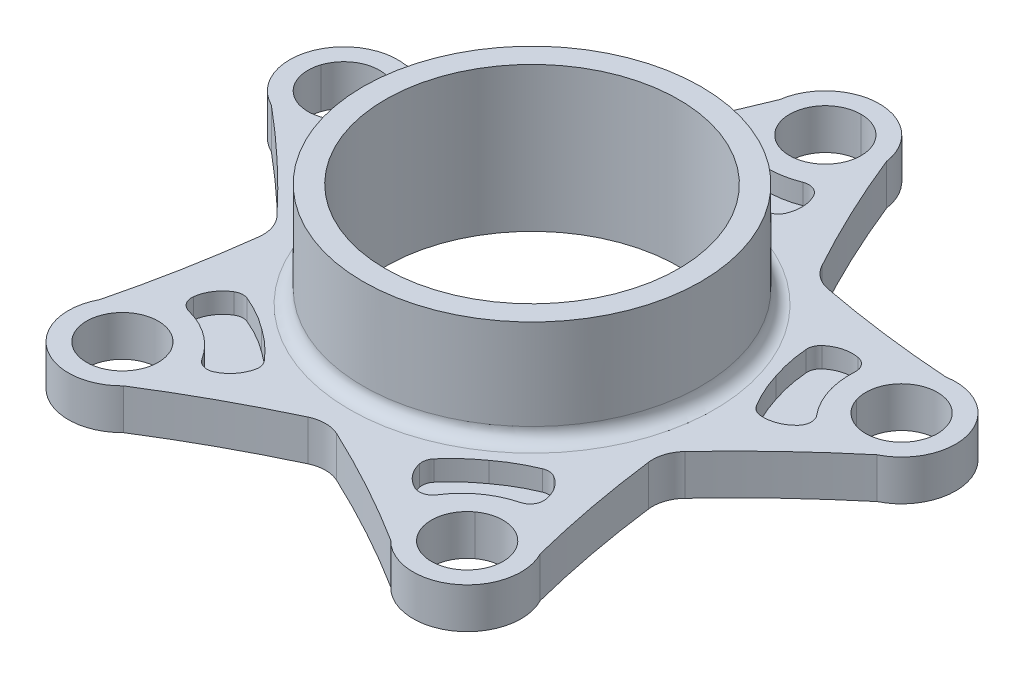
SolidWorks part; units mm, degrees
note: '?' marks a value the reader was unsure of.
ref_plane "Front Plane" through (0, 0, 0) normal (0, 0, 1) x (1, 0, 0)
ref_plane "Top Plane" through (0, 0, 0) normal (0, 1, 0) x (1, 0, 0)
ref_plane "Right Plane" through (0, 0, 0) normal (1, 0, 0) x (0, 0, -1)
sketch "Sketch1" plane through (0, 0, 0) normal (0, 1, 0) x (1, 0, 0)
  circle A0 centre (0, 0) radius 31.75
  dimension "D1" = 63.5
extrude "CenterCircleExtrude" add sketch "Sketch1" along normal blind 19.558 contours A0
sketch "Sketch2" plane through (0, 0, 0) normal (0, -1, 0) x (1, 0, 0)
  circle A0 centre (0, 0) radius 80.01
  dimension "D1" = 160.02
extrude "BaseExpand" add sketch "Sketch2" along normal blind 7.62
sketch "Sketch3" plane through (0, 19.558, 0) normal (0, 1, 0) x (1, 0, 0)
  circle A0 centre (0, 0) radius 27.559
  dimension "D1" = 55.118
extrude "CenterCut" cut sketch "Sketch3" against normal blind 27.178 contours A0
sketch "Sketch4" plane through (0, 0, 0) normal (0, 1, 0) x (1, 0, 0)
  line L0 (-52.4203, 17.0324) -> (0, 55.118) construction
  line L1 (-26.2102, 36.0752) -> (-18.6622, 25.6863) construction
  circle A0 centre (0, 55.118) radius 6.731
  circle A1 centre (52.4203, 17.0324) radius 6.731
  circle A2 centre (32.3975, -44.5914) radius 6.731
  circle A3 centre (-32.3975, -44.5914) radius 6.731
  circle A4 centre (-52.4203, 17.0324) radius 6.731
  circle A5 centre (0, 0) radius 31.75 construction
  point P14 (0, 0)
  dimension "D1" = 13.462
  dimension "D2" = 55.118
  dimension "D3" = 5
extrude "OuterCircleCut" cut sketch "Sketch4" against normal blind 7.62
sketch "Sketch8" plane through (0, 0, 0) normal (0, 1, 0) x (1, 0, 0)
  line L0 (-52.4203, 17.0324) -> (0, 55.118) construction
  line L1 (-26.2102, 36.0752) -> (-18.6622, 25.6863) construction
  line L2 (26.2102, 36.0752) -> (18.6622, 25.6863) construction
  line L3 (42.4089, -13.7795) -> (30.196, -9.8113) construction
  line L4 (0, -44.5914) -> (0, -31.75) construction
  line L5 (-42.4089, -13.7795) -> (-30.196, -9.8113) construction
  line L6 (0, -14.9479) -> (0, 14.9479) construction
  line L8 (0, 0) -> (10.16, 55.118) construction
  line L9 (10.16, 55.118) -> (-10.16, 55.118) construction
  circle A0 centre (-52.4203, 17.0324) radius 10.16
  circle A1 centre (0, 55.118) radius 10.16
  circle A2 centre (52.4203, 17.0324) radius 10.16
  circle A3 centre (32.3975, -44.5914) radius 10.16
  circle A4 centre (-32.3975, -44.5914) radius 10.16
  circle A5 centre (0, 0) radius 31.75 construction
  arc A6 (22.4362, 30.8807) -> (8.4002, 60.8331) centre (204.9622, 134.6791) cw
  arc A7 (-22.4362, 30.8807) -> (-8.4002, 60.8331) centre (-204.9622, 134.6791) ccw
  arc A8 (22.4362, 30.8807) -> (55.2599, 26.7875) centre (64.7506, 236.5488) ccw
  arc A9 (36.3025, -11.7954) -> (60.4515, 10.8094) centre (191.4243, -153.3125) cw
  arc A10 (36.3025, -11.7954) -> (42.5527, -44.2774) centre (244.9803, 11.5161) ccw
  arc A11 (0, -38.1707) -> (28.9609, -54.1525) centre (-86.6555, -229.4315) cw
  arc A12 (0, -38.1707) -> (-28.9609, -54.1525) centre (86.6555, -229.4315) ccw
  arc A13 (-36.3025, -11.7954) -> (-42.5527, -44.2774) centre (-244.9803, 11.5161) cw
  arc A14 (-36.3025, -11.7954) -> (-60.4515, 10.8094) centre (-191.4243, -153.3125) ccw
  arc A15 (-22.4362, 30.8807) -> (-55.2599, 26.7875) centre (-64.7506, 236.5488) cw
  point P14 (0, 0)
  point P27 (0, 0)
  point P63 (0, 0)
  point P72 (0, 0)
  dimension "D1" = 5
  dimension "D3" = 5
  dimension "D2" = 5
extrude "StarfishCut" cut sketch "Sketch8" against normal blind 7.62
sketch "Sketch14" plane through (0, 0, 0) normal (0, 1, 0) x (1, 0, 0)
  line L4 (0, -14.9479) -> (0, 14.9479) construction
  arc A0 (38.2121, 3.6164) -> (34.5928, 11.2399) centre (62.2856, 19.7161) cw
  arc A1 (33.0399, 19.5348) -> (34.5928, 11.2399) centre (61.9789, 20.6599) ccw
  arc A2 (41.5686, 21.0847) -> (33.0399, 19.5348) centre (38.134, 15.7437) ccw
  arc A25 (7.2074, 46.0496) -> (-7.2074, 46.0496) centre (0, 59.4776) cw
  arc A26 (-7.2074, 46.0496) -> (-8.3688, 37.4594) centre (-3.1891, 41.1327) ccw
  arc A27 (-8.3688, 37.4594) -> (0, 36.3731) centre (-0.4961, 65.3297) ccw
  arc A45 (8.3688, 37.4594) -> (0, 36.3731) centre (0.4961, 65.3297) cw
  arc A46 (7.2074, 46.0496) -> (8.3688, 37.4594) centre (3.1891, 41.1327) cw
  arc A47 (46.023, 7.3755) -> (41.5686, 21.0847) centre (56.5665, 18.3796) cw
  arc A48 (46.023, 7.3755) -> (38.2121, 3.6164) centre (40.105, 9.6777) cw
  arc A49 (15.2476, -35.2243) -> (21.3796, -29.4264) centre (37.9984, -53.1445) cw
  arc A50 (28.7886, -25.3862) -> (21.3796, -29.4264) centre (38.8012, -52.5612) ccw
  arc A51 (32.8982, -33.0185) -> (28.7886, -25.3862) centre (26.7572, -31.4026) ccw
  arc A52 (21.2364, -41.4913) -> (32.8982, -33.0185) centre (34.96, -48.1184) cw
  arc A53 (21.2364, -41.4913) -> (15.2476, -35.2243) centre (21.5972, -35.1516) cw
  arc A54 (-28.7886, -25.3862) -> (-21.3796, -29.4264) centre (-38.8012, -52.5612) cw
  arc A55 (-15.2476, -35.2243) -> (-21.3796, -29.4264) centre (-37.9984, -53.1445) ccw
  arc A56 (-21.2364, -41.4913) -> (-15.2476, -35.2243) centre (-21.5972, -35.1516) ccw
  arc A57 (-32.8982, -33.0185) -> (-21.2364, -41.4913) centre (-34.96, -48.1184) cw
  arc A58 (-32.8982, -33.0185) -> (-28.7886, -25.3862) centre (-26.7572, -31.4026) cw
  arc A59 (-33.0399, 19.5348) -> (-34.5928, 11.2399) centre (-61.9789, 20.6599) cw
  arc A60 (-38.2121, 3.6164) -> (-34.5928, 11.2399) centre (-62.2856, 19.7161) ccw
  arc A61 (-46.023, 7.3755) -> (-38.2121, 3.6164) centre (-40.105, 9.6777) ccw
  arc A62 (-41.5686, 21.0847) -> (-46.023, 7.3755) centre (-56.5665, 18.3796) cw
  arc A63 (-41.5686, 21.0847) -> (-33.0399, 19.5348) centre (-38.134, 15.7437) cw
  point P34 (0, 0)
  point P51 (0, 0)
  point P61 (0, 0)
  point P97 (0, 0)
  dimension "D1" = 6.35
  dimension "D2" = 15.24
  dimension "D4" = 5
  dimension "D3" = 28.9609
extrude "Batman Cut" cut sketch "Sketch14" against normal blind 3.81
fillet "Fillet11" radius 2.54 20 edges at (21.2364, -1.905, 41.4913) (32.8982, -1.905, 33.0185) (28.7886, -1.905, 25.3862) (15.2476, -1.905, 35.2243) (-21.2364, -1.905, 41.4913) (-32.8982, -1.905, 33.0185) (-15.2476, -1.905, 35.2243) (-28.7886, -1.905, 25.3862) (-38.2121, -1.905, -3.6164) (-46.023, -1.905, -7.3755) (-33.0399, -1.905, -19.5348) (-41.5686, -1.905, -21.0847) (38.2121, -1.905, -3.6164) (33.0399, -1.905, -19.5348) (46.023, -1.905, -7.3755) (41.5686, -1.905, -21.0847) (-8.3688, -1.905, -37.4594) (8.3688, -1.905, -37.4594) (-7.2074, -1.905, -46.0496) (7.2074, -1.905, -46.0496)
ref_axis "Axis1" through (0, -7.62, 0) along (0, 1, 0)?
fillet "Fillet12" radius 6.35 5 edges at (-36.3025, -3.81, 11.7954) (0, -3.81, 38.1707) (36.3025, -3.81, 11.7954) (22.4362, -3.81, -30.8807) (-22.4362, -3.81, -30.8807)
ref_plane "Plane1" through (0, 0, 0) normal (-0.309, 0, 0.9511) x (0.9511, 0, 0.309)
ref_plane "Plane2" through (0, 0, 0) normal (-0.809, 0, -0.5878) x (-0.5878, 0, 0.809)
ref_plane "Plane3" through (0, 0, 0) normal (-0.809, 0, 0.5878) x (0.5878, 0, 0.809)
ref_plane "Plane4" through (0, 0, 0) normal (0.309, 0, 0.9511) x (0.9511, 0, -0.309)
split line "Split Line1"
split line "Split Line2"
split line "Split Line3"
split line "Split Line4"
split line "Split Line5"
fillet "Fillet13" radius 2.54 1 edges at (0, 0, 31.75)
